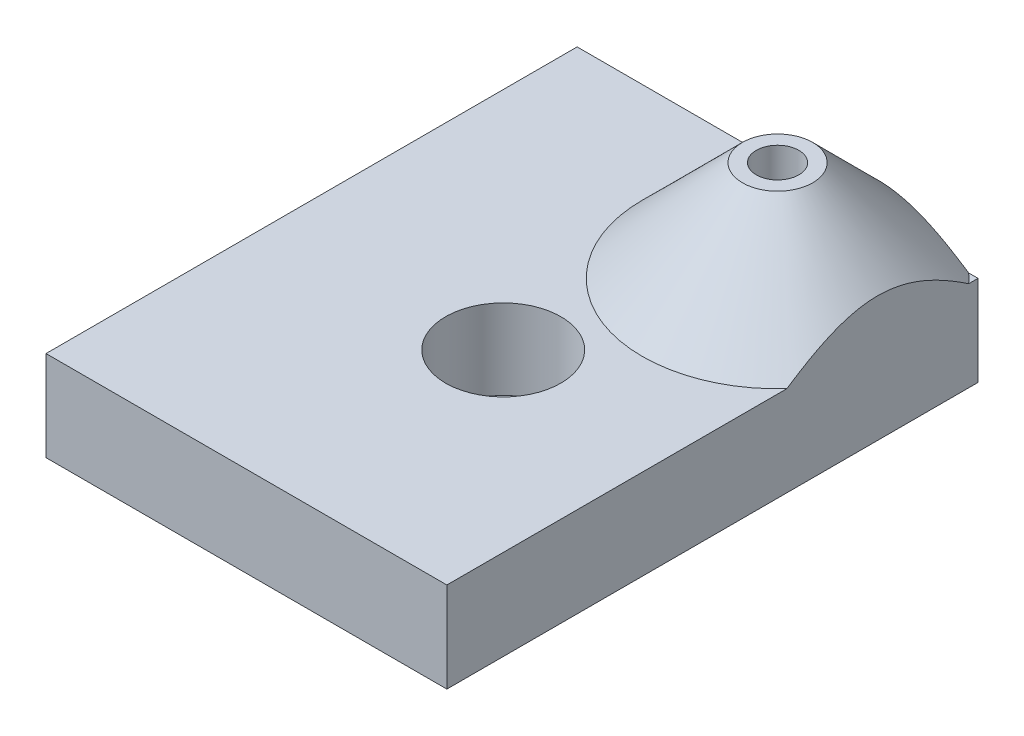
SolidWorks part; units mm, degrees
ref_plane "Front Plane" through (0, 0, 0) normal (0, 0, 1) x (1, 0, 0)
ref_plane "Top Plane" through (0, 0, 0) normal (0, 1, 0) x (1, 0, 0)
ref_plane "Right Plane" through (0, 0, 0) normal (1, 0, 0) x (0, 0, -1)
sketch "Sketch1" plane through (0, 0, 0) normal (0, 1, 0) x (1, 0, 0)
  line L0 (-358.727, 0) -> (17577.6232, 0) construction
  line L1 (0, -358.727) -> (0, 17577.6232) construction
  line L3 (-20, -24) -> (20, -24)
  line L4 (-20, -24) -> (-20, 24)
  line L5 (-20, 24) -> (20, 24)
  line L6 (20, -24) -> (20, 24)
  line L7 (-20, -24) -> (20, 24) construction
  line L8 (-20, 24) -> (20, -24) construction
  point P4 (0, 0)
  dimension "D1" = 40
  dimension "D2" = 48
extrude "Boss-Extrude1" add sketch "Sketch1" along normal blind 9
sketch "Sketch2" plane through (0, 0, 0) normal (0, -1, 0) x (1, 0, 0)
  line L0 (20, 24) -> (20, -24) construction
  line L1 (-20, 24) -> (20, 24) construction
  circle A0 centre (2.5, 0.875) radius 2.625
  point P6 (6.0573, 2.678)
  dimension "D1" = 5.25
  dimension "D2" = 17.5
  dimension "D3" = 23.125
extrude "Cut-Extrude1" cut sketch "Sketch2" against normal through all both and the other way through all
sketch "Sketch3" plane through (0, 9, 0) normal (0, 1, 0) x (1, 0, 0)
  circle A0 centre (2.5, -0.875) radius 5.75
  dimension "D1" = 11.5
extrude "Cut-Extrude2" cut sketch "Sketch3" against normal blind 8
sketch "Sketch5" plane through (0, 9, 0) normal (0, 1, 0) x (1, 0, 0)
  line L0 (-20, -24) -> (20, -24) construction
  line L1 (20, -24) -> (20, 24) construction
  circle A0 centre (10, 19) radius 3.5
  point P4 (0, 0)
  dimension "D1" = 7
  dimension "D2" = 43
  dimension "D3" = 10
extrude "Boss-Extrude2" add sketch "Sketch5" along normal blind 10
sketch "Sketch6" plane through (0, 0, -24) normal (0, 0, -1) x (-1, 0, 0)
  line L1 (-20, 9) -> (20, 9)
  line L2 (-20, 9) -> (-20, 0)
  line L3 (-20, 0) -> (20, 0)
  line L4 (20, 9) -> (20, 0)
extrude "Boss-Extrude3" add sketch "Sketch6" along normal blind 5
chamfer "Chamfer1" distance 10 angle 45 1 edges at (10, 9, -22.5)
sketch "Sketch7" plane through (0, 19, 0) normal (0, 1, 0) x (1, 0, 0)
  circle A0 centre (10, 19) radius 2.125
  dimension "D1" = 4.25
extrude "Cut-Extrude3" cut sketch "Sketch7" against normal through all both and the other way through all
sketch "Sketch8" plane through (0, 0, 0) normal (0, -1, 0) x (1, 0, 0)
  line L0 (-987.625, -19) -> (49012.375, -19) construction
  line L1 (7.625, -22.625) -> (12.375, -22.625)
  line L2 (7.625, -22.625) -> (7.625, -15.375)
  line L3 (7.625, -15.375) -> (12.375, -15.375)
  line L4 (12.375, -22.625) -> (12.375, -15.375)
  line L5 (7.625, -22.625) -> (12.375, -15.375) construction
  line L6 (7.625, -15.375) -> (12.375, -22.625) construction
  line L7 (12.375, -15.375) -> (14.4679, -19)
  line L8 (14.4679, -19) -> (12.375, -22.625)
  line L9 (7.625, -22.625) -> (5.5321, -19)
  line L10 (7.625, -15.375) -> (5.5321, -19)
  point P0 (10, -19)
  point P9 (12.375, -19)
  circle M7 centre (10, -19) radius 2.125
  dimension "D1" = 4.75
  dimension "D2" = 7.25
  dimension "D3" = 240
  dimension "D4" = 240
extrude "Cut-Extrude4" cut sketch "Sketch8" against normal blind 11 contours L1 L4 L3 L2 M7 | L2 L10 L9 | L8 L7 L4 region at (7.7117, 0, -19) region at (6.9274, 0, -19) region at (13.0726, 0, -19)
